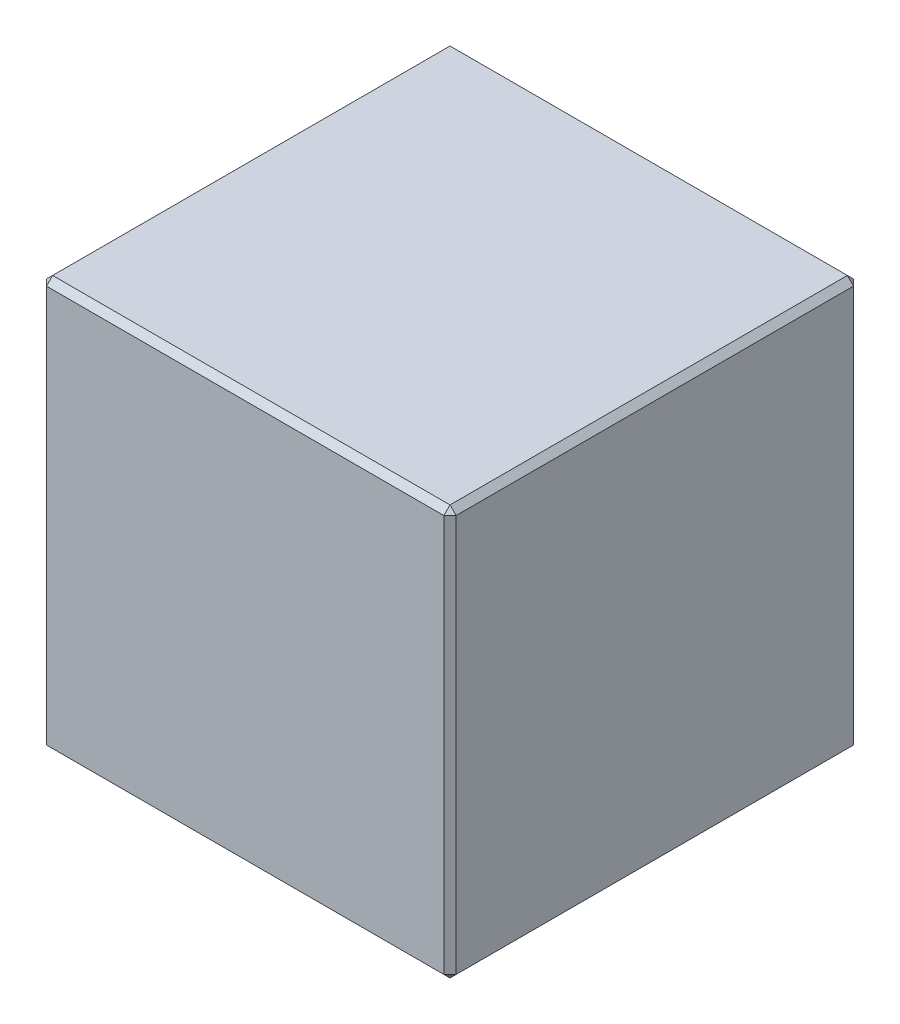
SolidWorks part; units mm, degrees
ref_plane "Front" through (0, 0, 0) normal (0, 0, 1) x (1, 0, 0)
ref_plane "Top" through (0, 0, 0) normal (0, 1, 0) x (1, 0, 0)
ref_plane "Right" through (0, 0, 0) normal (1, 0, 0) x (0, 0, -1)
ref_axis "Z AXIS" through (0, 0, 10.1914) along (0, 0, -1)
ref_axis "Y AXIS" through (0, 16.6631, 0) along (0, -1, 0)
ref_axis "X AXIS" through (18.31, 0, 0) along (-1, 0, 0)
sketch "Sketch1" plane through (0, 0, 0) normal (0, 1, 0) x (1, 0, 0)
  line L1 (0, 0) -> (40, 0)
  line L2 (0, 0) -> (0, 40)
  line L3 (0, 40) -> (40, 40)
  line L4 (40, 0) -> (40, 40)
  dimension "D1" = 40
extrude "Boss-Extrude1" add sketch "Sketch1" along normal blind 40
chamfer "Chamfer1" distance 0.6 angle 45 12 edges at (40, 0, -20) (0, 0, -20) (40, 40, -20) (40, 20, -40) (20, 40, -40) (20, 0, -40) (0, 20, -40) (0, 40, -20) (0, 20, 0) (20, 40, 0) (40, 20, 0) (20, 0, 0)
